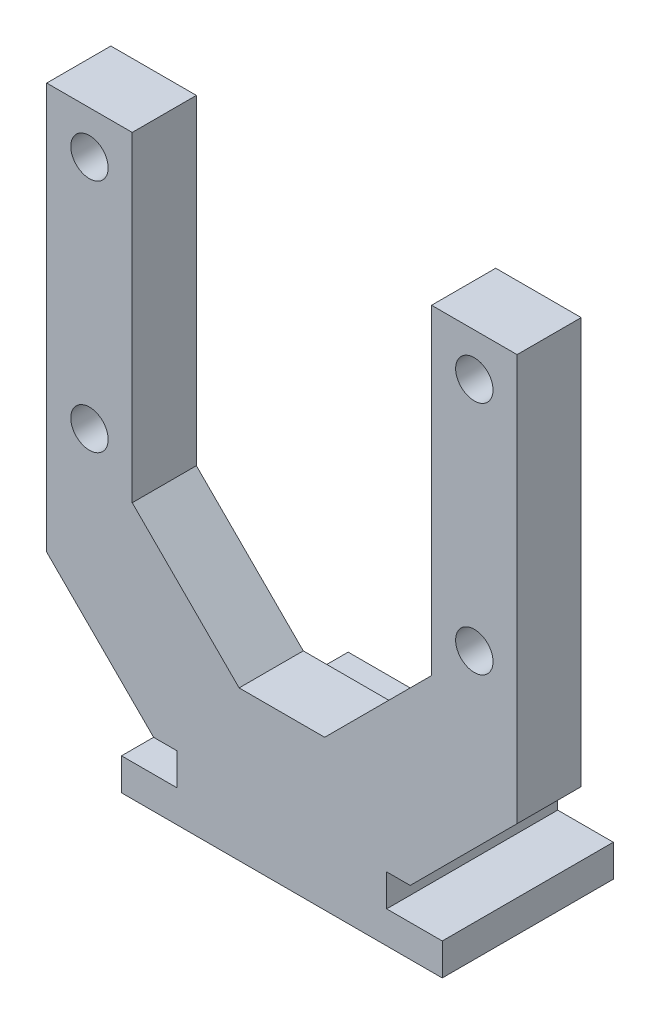
SolidWorks part; units mm, degrees
ref_plane "Front Plane" through (0, 0, 0) normal (0, 0, 1) x (1, 0, 0)
ref_plane "Top Plane" through (0, 0, 0) normal (0, 1, 0) x (1, 0, 0)
ref_plane "Right Plane" through (0, 0, 0) normal (1, 0, 0) x (0, 0, -1)
sketch "Sketch1" plane through (0, 0, 0) normal (0, 0, 1) x (1, 0, 0)
  line L1 (-7.5, 0) -> (7.5, 0)
  line L3 (4.9, 3) -> (11, 3)
  line L4 (11, 3) -> (11, 27)
  line L5 (11, 27) -> (7, 27)
  line L6 (-11, 27) -> (-11, 3)
  line L7 (-11, 3) -> (-4.9, 3)
  line L8 (-7, 27) -> (-7, 7)
  line L9 (-7, 7) -> (7, 7)
  line L10 (7, 7) -> (7, 27)
  line L11 (-7, 27) -> (-11, 27)
  line L12 (-9, 25) -> (9, 25) construction
  line L13 (9, 25) -> (9, 14) construction
  line L14 (-4.9, 3) -> (-4.9, 1.5)
  line L15 (-4.9, 1.5) -> (-7.5, 1.5)
  line L16 (-7.5, 1.5) -> (-7.5, 0)
  line L17 (4.9, 3) -> (4.9, 1.5)
  line L18 (4.9, 1.5) -> (7.5, 1.5)
  line L19 (7.5, 1.5) -> (7.5, 0)
  line L20 (4.9, 3) -> (-4.9, 3)
  circle A0 centre (-9, 25) radius 0.875
  circle A1 centre (9, 25) radius 0.875
  circle A2 centre (9, 14) radius 0.875
  circle A3 centre (-9, 14) radius 0.875
  point P0 (0, 0)
  point P9 (0, 7)
  point P23 (0, 25)
  point P27 (9, 19.5)
  point P29 (9, 27)
  dimension "D1" = 1.75
  dimension "D2" = 11
  dimension "D3" = 18
  dimension "D4" = 9.8
  dimension "D5" = 3
  dimension "D6" = 1.5
  dimension "D7" = 15
  dimension "D8" = 18
  dimension "D9" = 4
  dimension "D10" = 2
  dimension "D11" = 4
extrude "Boss-Extrude1" add sketch "Sketch1" along normal blind 3 contours L17 L20 L14 L15 L16 L1 L19 L18 | L20 L3 L4 L5 L10 L9 L8 L11 L6 L7 A3 A2 A1 A0 region at (0, 1.3427, 0) region at (-7.95, 3.3256, 0)
chamfer "Chamfer1" distance 5 angle 45 4 edges at (7, 7, 1.5) (-7, 7, 1.5) (-11, 3, 1.5) (11, 3, 1.5)
extrude "Boss-Extrude2" add sketch "Sketch1<4>" against normal blind 5 contours L17 L20 L14 L15 L16 L1 L19 L18 region at (0, 1.3427, 0)
sketch "Sketch1<4>" plane through (0, 0, 0) normal (0, 0, 1) x (1, 0, 0) same geometry as "Sketch1"
sketch "Sketch2" plane through (0, 3, 0) normal (0, 1, 0) x (1, 0, 0)
  line L0 (4.9, 5) -> (-4.9, 5) construction
  circle A0 centre (0, 3) radius 1.5
  point P2 (0, 3.0276)
  point P3 (0, 0)
  point P5 (0, 0)
  dimension "D1" = 3
  dimension "D2" = 2
extrude "Cut-Extrude1" cut sketch "Sketch2" against normal through all
chamfer "Chamfer2" distance 1 angle 45 1 edges at (0, 3, 0)
